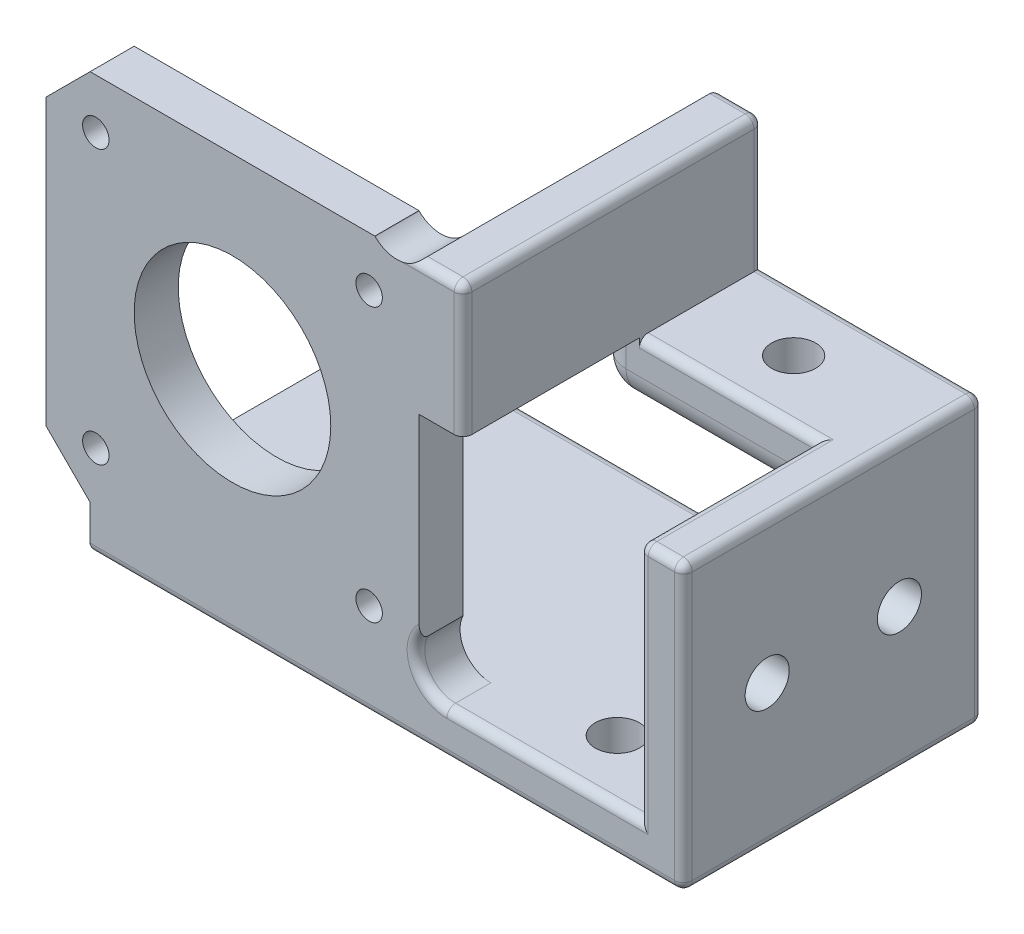
SolidWorks part; units mm, degrees
ref_plane "정면" through (0, 0, 0) normal (0, 0, 1) x (1, 0, 0)
ref_plane "윗면" through (0, 0, 0) normal (0, 1, 0) x (1, 0, 0)
ref_plane "우측면" through (0, 0, 0) normal (1, 0, 0) x (0, 0, -1)
sketch "스케치1" plane through (0, 0, 0) normal (0, 0, 1) x (1, 0, 0)
  line L0 (-21.15, 16.15) -> (-16.15, 21.15)
  line L1 (-16.15, -21.15) -> (16.15, -21.15)
  line L2 (-21.15, -16.15) -> (-21.15, 16.15)
  line L3 (-16.15, 21.15) -> (16.15, 21.15)
  line L4 (21.15, -16.15) -> (21.15, 16.15)
  line L5 (-21.15, -21.15) -> (21.15, 21.15) construction
  line L6 (-21.15, 21.15) -> (21.15, -21.15) construction
  line L7 (16.15, 21.15) -> (21.15, 16.15)
  line L8 (16.15, -21.15) -> (21.15, -16.15)
  line L9 (-21.15, -16.15) -> (-16.15, -21.15)
  line L10 (0, 15.5) -> (0, -15.5) construction
  line L11 (-15.5, -15.5) -> (15.5, -15.5) construction
  line L12 (-15.5, -15.5) -> (-15.5, 15.5) construction
  line L13 (-15.5, 15.5) -> (15.5, 15.5) construction
  line L14 (15.5, -15.5) -> (15.5, 15.5) construction
  line L15 (-15.5, -15.5) -> (15.5, 15.5) construction
  line L16 (-15.5, 15.5) -> (15.5, -15.5) construction
  line L17 (-15.5, 0) -> (15.5, 0) construction
  circle A0 centre (-15.5, 15.5) radius 1.5
  circle A1 centre (15.5, 15.5) radius 1.5
  circle A2 centre (15.5, -15.5) radius 1.5
  circle A3 centre (-15.5, -15.5) radius 1.5
  circle A4 centre (0, 0) radius 11.15
  circle A5 centre (0, 0) radius 2.5
  point P0 (0, 0)
  point P5 (17.7284, 18.812)
  point P6 (0, 0)
  point P15 (0, 0)
  dimension "D2" = 22.3
  dimension "D3" = 3
  dimension "D7" = 5
  dimension "D1" = 42.3
  dimension "D4" = 31
  dimension "D5" = 5
  dimension "D6" = 5
extrude "보스-돌출1" add sketch "스케치1" along normal blind 5 contours L2 L9 L1 L8 L4 L7 L3 L0 A4 A1 A0 A2 A3 region at (-18.227, 18.227, 0)
sketch "스케치2" plane through (21.15, 0, 0) normal (1, 0, 0) x (0, 0, -1)
  line L0 (0, -16.15) -> (0, 16.15) construction
  line L1 (-5, 16.15) -> (-5, -16.15) construction
  line L2 (-5, -16.15) -> (0, -16.15) construction
  line L3 (0, 16.15) -> (0, 21.15) construction
  line L4 (0, 21.15) -> (-5, 21.15) construction
  line L5 (-5, 21.15) -> (-5, 16.15) construction
  line L6 (0, -16.15) -> (0, 16.15)
  line L7 (-5, 16.15) -> (-5, -16.15)
  line L8 (-5, -16.15) -> (0, -16.15)
  line L9 (0, 16.15) -> (0, 21.15)
  line L10 (0, 21.15) -> (-5, 21.15)
  line L11 (-5, 21.15) -> (-5, 16.15)
  line L12 (15, 21.15) -> (15, -16.15)
  line L13 (-5, 21.15) -> (29, 21.15)
  line L14 (-5, 21.15) -> (-5, 6.15)
  line L15 (-5, 6.15) -> (29, 6.15)
  line L16 (29, 21.15) -> (29, 6.15)
  line L17 (-5, 21.15) -> (29, 21.15)
  line L18 (-5, 21.15) -> (-5, -16.15)
  line L19 (-5, -16.15) -> (29, -16.15)
  line L20 (29, 21.15) -> (29, -16.15)
  line L22 (-5, 21.15) -> (29, 21.15)
  line L23 (-5, 21.15) -> (-5, 16.15)
  line L24 (-5, 16.15) -> (29, 16.15)
  line L25 (29, 21.15) -> (29, 16.15)
  line L26 (15, 6.15) -> (29, 6.15)
  line L27 (15, 6.15) -> (15, -1.15)
  line L28 (15, -1.15) -> (29, -1.15)
  line L29 (29, 6.15) -> (29, -1.15)
  line L33 (0, -21.15) -> (0, -16.15)
  line L34 (0, -16.15) -> (-5, -16.15)
  line L35 (-5, -16.15) -> (-5, -21.15)
  line L36 (-5, -21.15) -> (0, -21.15)
  line L37 (0, -21.15) -> (0, -16.15)
  line L38 (0, -16.15) -> (-5, -16.15)
  line L39 (-5, -16.15) -> (-5, -21.15)
  line L40 (-5, -21.15) -> (0, -21.15)
  line M5 (0, 16.15) -> (-5, 16.15)
  line M6 (-5, 16.15) -> (-5, -16.15)
  dimension "D1" = 20
  dimension "D2" = 34
  dimension "D3" = 15
  dimension "D4" = 0
extrude "보스-돌출2" add sketch "스케치2" along normal blind 5 contours L24 L12 L15 L20 | L24 L6 L15 L12 | L15 L6 M6 M5 | L10 L11 L9 M5 | L9 L24 L12 L13 | L12 L24 L16 L13 region at (21.15, 11.15, 2.5) region at (21.15, 11.15, -7.5) region at (21.15, 18.65, 2.5) region at (21.15, 18.65, -7.5) region at (21.15, 11.15, -22) region at (21.15, 18.65, -22)
extrude "보스-돌출6" add sketch "스케치2<3>" along normal blind 25 contours L12 L28 L20 L15 region at (21.15, 2.5, -22)
sketch "스케치2<3>" plane through (21.15, 0, 0) normal (1, 0, 0) x (0, 0, -1) same geometry as "스케치2"
sketch "스케치6" plane through (46.15, 0, 0) normal (1, 0, 0) x (0, 0, -1)
  line L1 (29, 6.15) -> (-5, 6.15)
  line L2 (29, 6.15) -> (29, -21.15)
  line L3 (29, -21.15) -> (-5, -21.15)
  line L4 (-5, 6.15) -> (-5, -21.15)
  line L8 (15, 6.15) -> (15, -1.15)
  line L9 (15, -1.15) -> (29, -1.15)
  line L10 (29, -1.15) -> (29, 6.15)
  line L11 (29, 6.15) -> (15, 6.15)
  line L12 (15, 6.15) -> (15, -1.15)
  line L13 (15, -1.15) -> (29, -1.15)
  line L14 (29, -1.15) -> (29, 6.15)
  line L15 (29, 6.15) -> (15, 6.15)
  line M1 (15, 6.15) -> (15, -1.15)
  line M2 (15, -1.15) -> (29, -1.15)
  line M3 (29, -1.15) -> (29, 6.15)
  line M4 (29, 6.15) -> (15, 6.15)
  dimension "D1" = 0
extrude "보스-돌출7" add sketch "스케치6" along normal blind 5 contours M4 M1 M2 M3 | L1 L4 L3 L2 M2 M1 region at (46.15, 2.5, -22) region at (46.15, -8.7373, -10.7627)
sketch "스케치7" plane through (0, -21.15, 0) normal (0, -1, 0) x (1, 0, 0)
  line L0 (-16.15, 5) -> (-16.15, 0) construction
  line L1 (51.15, 5) -> (-16.15, 5)
  line L2 (51.15, 5) -> (51.15, -29)
  line L3 (51.15, -29) -> (-16.15, -29)
  line L4 (-16.15, 5) -> (-16.15, -29)
  line L5 (51.15, -29) -> (46.15, -29) construction
extrude "보스-돌출8" add sketch "스케치7" along normal blind 5
fillet "필렛9" radius 3.5 1 edges
fillet "필렛8" radius 1 24 edges at (-16.15, -23.65, -29) (38.65, 6.15, -29) (26.15, 13.65, -29) (23.65, 21.15, -29) (21.15, 10, -29) (51.15, -10, -29) (51.15, -10, 5) (51.15, 6.15, -12) (17.5, -26.15, -29) (-16.15, -26.15, -12) (17.5, -26.15, 5) (51.15, -26.15, -12) (26.15, 21.15, -12) (23.65, 21.15, 5) (26.15, 13.65, 5) (48.65, 6.15, 5) (21.3542, -19.5208, 5)
fillet "필렛10" radius 3.5 1 edges
fillet "필렛11" radius 3.5 4 edges at (21.4429, -0.8571, -28.7071) (33.65, -1.15, -15) (21.15, -1.15, -21.5) (21.15, 2.5, -15)
sketch "스케치8" plane through (0, 6.15, 0) normal (0, 1, 0) x (1, 0, 0)
  line L0 (36.65, 28) -> (36.65, 16) construction
  line L1 (47.15, 16) -> (26.15, 16)
  line L2 (47.15, 16) -> (47.15, 28)
  line L3 (47.15, 28) -> (26.15, 28)
  line L4 (26.15, 16) -> (26.15, 28)
  line L5 (47.15, 22) -> (26.15, 22) construction
  line L6 (26.15, 28) -> (26.15, 16)
  line L7 (26.15, 16) -> (47.15, 16)
  line L8 (47.15, 16) -> (47.15, -4)
  line L9 (47.15, -4) -> (50.15, -4)
  line L10 (50.15, -4) -> (50.15, 28)
  line L11 (50.15, 28) -> (26.15, 28)
  line L12 (26.15, 28) -> (26.15, 16)
  line L13 (26.15, 16) -> (47.15, 16)
  line L14 (47.15, 16) -> (47.15, -4)
  line L15 (47.15, -4) -> (50.15, -4)
  line L16 (50.15, -4) -> (50.15, 28)
  line L17 (50.15, 28) -> (26.15, 28)
  circle A0 centre (36.65, 22) radius 2.5
  dimension "D2" = 5
  dimension "D1" = 0
extrude "컷-돌출1" cut sketch "스케치8" against normal blind 5 contours A0
sketch "스케치9" plane through (51.15, 0, 0) normal (1, 0, 0) x (0, 0, -1)
  line L0 (12, 5.15) -> (12, -25.15) construction
  line L1 (-4, -10) -> (28, -10) construction
  line L4 (28, -25.15) -> (28, 5.15)
  line L5 (28, 5.15) -> (-4, 5.15)
  line L6 (-4, 5.15) -> (-4, -25.15)
  line L7 (-4, -25.15) -> (28, -25.15)
  line L8 (28, -25.15) -> (28, 5.15)
  line L9 (28, 5.15) -> (-4, 5.15)
  line L10 (-4, 5.15) -> (-4, -25.15)
  line L11 (-4, -25.15) -> (28, -25.15)
  circle A0 centre (4.5, -10) radius 2.5
  circle A1 centre (19.5, -10) radius 2.5
  dimension "D2" = 5
  dimension "D3" = 15
  dimension "D1" = 0
extrude "컷-돌출2" cut sketch "스케치9" against normal blind 5 contours A0 | A1 region at (51.15, -10, -4.5) region at (51.15, -10, -19.5)
sketch "스케치10" plane through (0, -21.15, 0) normal (0, 1, 0) x (1, 0, 0)
  line L0 (36.65, 28) -> (36.65, -4) construction
  line L1 (26.15, 28) -> (47.15, 28)
  line L2 (26.15, 28) -> (47.15, 28)
  line L3 (26.15, -4) -> (47.15, -4)
  line L4 (47.15, 28) -> (47.15, -4)
  line L5 (26.15, 28) -> (26.15, -4)
  line L6 (26.15, 28) -> (26.15, 16)
  line L7 (26.15, 16) -> (47.15, 16)
  line L8 (47.15, 16) -> (47.15, -4)
  line L9 (47.15, -4) -> (50.15, -4)
  line L10 (50.15, -4) -> (50.15, 28)
  line L11 (50.15, 28) -> (26.15, 28)
  line L12 (26.15, 28) -> (26.15, 16)
  line L13 (26.15, 16) -> (47.15, 16)
  line L14 (47.15, 16) -> (47.15, -4)
  line L15 (47.15, -4) -> (50.15, -4)
  line L16 (50.15, -4) -> (50.15, 28)
  line L17 (50.15, 28) -> (26.15, 28)
  line L18 (26.15, -4) -> (47.15, -4)
  line L19 (47.15, 28) -> (47.15, -4)
  circle A0 centre (36.65, 22) radius 2.5 construction
  circle A1 centre (36.65, 22) radius 2.5
  circle A2 centre (36.65, 12) radius 2.5
  circle A3 centre (36.65, 2) radius 2.5
  dimension "D2" = 5
  dimension "D3" = 10
  dimension "D4" = 10
  dimension "D1" = 0
extrude "컷-돌출3" cut sketch "스케치10" against normal blind 5 contours A1 | A2 | A3
